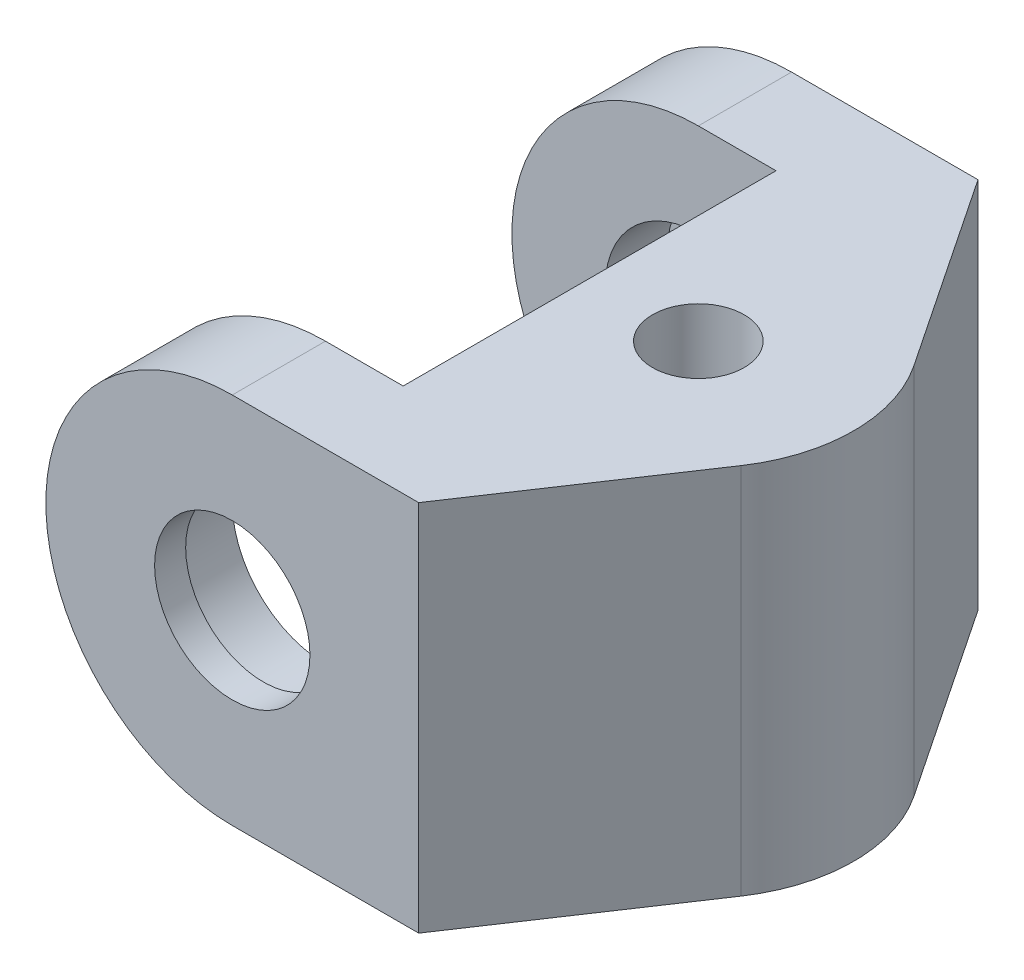
SolidWorks part; units mm, degrees
ref_plane "Front Plane" through (0, 0, 0) normal (0, 0, 1) x (1, 0, 0)
ref_plane "Top Plane" through (0, 0, 0) normal (0, 1, 0) x (1, 0, 0)
ref_plane "Right Plane" through (0, 0, 0) normal (1, 0, 0) x (0, 0, -1)
sketch "Sketch1" plane through (0, 0, 0) normal (0, 0, 1) x (1, 0, 0)
  circle A1 centre (-6, 0) radius 6
  circle A2 centre (-6, 0) radius 2.5
  point P4 (-9.8932, 1.4578)
  dimension "D2" = 5
  dimension "D3" = 12
  dimension "D1" = 6
extrude "Boss-Extrude1" add sketch "Sketch1" along normal mid plane 18
sketch "Sketch2" plane through (0, 0, 0) normal (0, 1, 0) x (1, 0, 0)
  circle A0 centre (0, 0) radius 1.475
  circle A1 centre (0, 0) radius 5
  dimension "D1" = 10
  dimension "D2" = 2.95
extrude "Boss-Extrude2" add sketch "Sketch2" along normal mid plane 12
sketch "Sketch4" plane through (0, 0, 0) normal (0, 1, 0) x (1, 0, 0)
  line L0 (-6, 9) -> (-6, -9)
  line L1 (0, 9) -> (-12, 9) construction
  line L2 (-12, -9) -> (0, -9) construction
  line L3 (-6, -9) -> (0, -9)
  line L4 (0, -9) -> (4.1574, -2.7778)
  line L5 (4.1574, 2.7778) -> (0, 9)
  line L6 (0, 9) -> (-6, 9)
  line L7 (0, 5) -> (0, 9) construction
  circle A0 centre (0, 0) radius 5 construction
  arc A1 (4.1574, -2.7778) -> (4.1574, 2.7778) centre (0, 0) ccw
  point P6 (-1, 9)
extrude "Boss-Extrude3" add sketch "Sketch4" along normal mid plane 12
sketch "Sketch3" plane through (0, 0, 0) normal (0, 1, 0) x (1, 0, 0)
  line L0 (-6, 12.2341) -> (-6, -14.1605) construction
  line L1 (-3.5, 8) -> (-3.5, 9)
  line L4 (-3.5, 8) -> (-3, 8)
  line L5 (-3, 8) -> (-3, 6)
  line L6 (-3, 6) -> (-1.5, 6)
  line L8 (-1.5, -6) -> (-3, -6)
  line L9 (-3, -6) -> (-3, -8)
  line L10 (-3, -8) -> (-3.5, -8)
  line L11 (-6, -9) -> (-6, 9)
  line L12 (-6, 9) -> (-8.5, 9) construction
  line L13 (0, 0) -> (-16.9033, 0) construction
  line L15 (0, 9) -> (-6, 9) construction
  line L16 (-3.5, 9) -> (-6, 9)
  line L17 (-3.5, -8) -> (-3.5, -9)
  line L18 (-3.5, -9) -> (-6, -9)
  line L19 (-1.5, 6) -> (-1.5, -6)
  line L20 (-6, 9) -> (-6, -9) construction
  dimension "D1" = 6
  dimension "D2" = 1
  dimension "D3" = 2
  dimension "D6" = 0.5
  dimension "D7" = 9
revolve "Cut-Revolve1" cut sketch "Sketch3" angle 360 about L0
sketch "Sketch5" plane through (0, 0, 0) normal (0, 1, 0) x (1, 0, 0)
  line L0 (-3.5, 6) -> (-3.5, -6)
  line L1 (-3.5, -6) -> (-12, -6)
  line L2 (-12, -6) -> (-12, 6)
  line L3 (-12, 6) -> (-3.5, 6)
  line L4 (-12, 9) -> (-12, -9) construction
  line L5 (-9, 6) -> (-3, 6) construction
  line L6 (-6, 9) -> (-6, -9) construction
  line L7 (0, 0) -> (-13.9863, 0) construction
  circle A0 centre (0, 0) radius 1.475
  circle A2 centre (0, 0) radius 1.475 construction
  dimension "D1" = 2.5
extrude "Cut-Extrude2" cut sketch "Sketch5" against normal through all both and the other way through all
combine bodies "Combine1" [suppressed] operation type add bodies to combine 111 112 111 111
